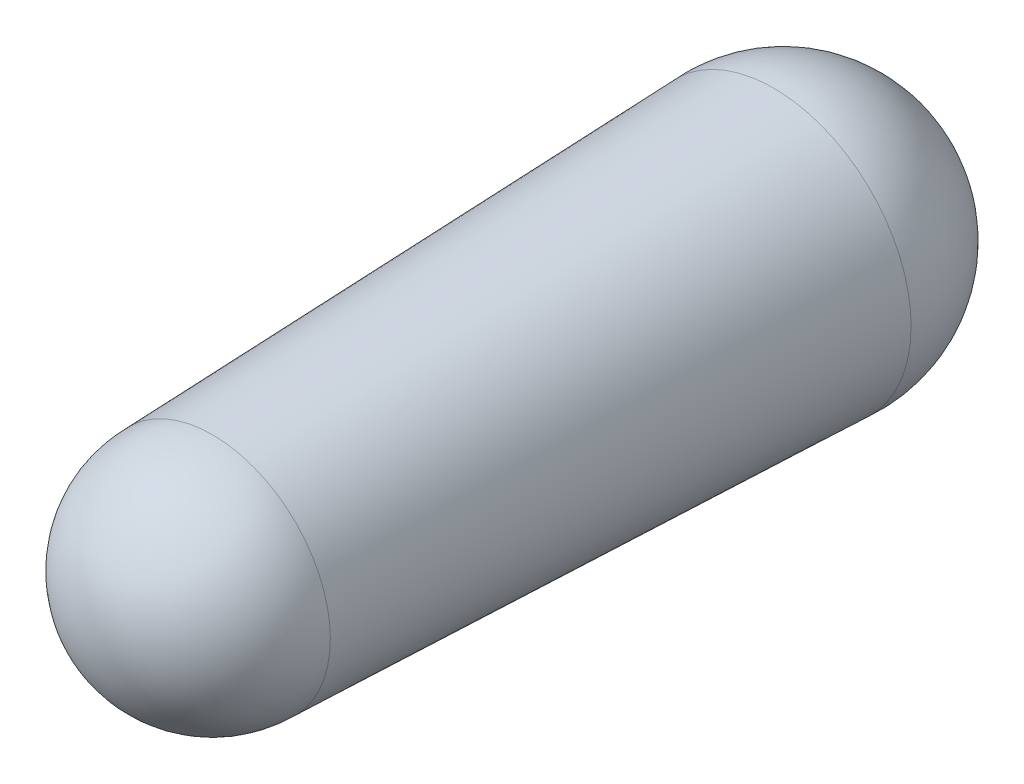
SolidWorks part; units mm, degrees
material "1060 Alloy"
ref_plane "Front Plane" through (0, 0, 0) normal (0, 0, 1) x (1, 0, 0)
ref_plane "Top Plane" through (0, 0, 0) normal (0, 1, 0) x (1, 0, 0)
ref_plane "Right Plane" through (0, 0, 0) normal (1, 0, 0) x (0, 0, -1)
sketch "Sketch1" plane through (0, 0, 0) normal (0, 0, 1) x (1, 0, 0)
  line L0 (0, 1.69) -> (0, -1.69) construction
  line L1 (0, 1.69) -> (0, -1.69)
  arc A0 (0, -1.69) -> (0, 1.69) centre (0, 0) ccw
  dimension "D1" = 3.38
revolve "Revolve1" add sketch "Sketch1" angle 360 about L0
sketch "Sketch2" plane through (0, 0, 0) normal (0, 0, 1) x (1, 0, 0)
  circle A0 centre (0, 0) radius 1.69
  circle A1 centre (0, 0) radius 1.69 construction
extrude "Boss-Extrude1" add sketch "Sketch2" along normal blind 7 draft 2
sketch "Sketch3" plane through (0, 0, 7) normal (0, 0, 1) x (1, 0, 0)
  line L0 (0, 1.4456) -> (0, -1.4456) construction
  line L1 (0, 1.4456) -> (0, -1.4456)
  arc A0 (0, -1.4456) -> (0, 1.4456) centre (0, 0) ccw
  circle A1 centre (0, 0) radius 1.4456 construction
revolve "Revolve2" add sketch "Sketch3" angle 360 about L0
